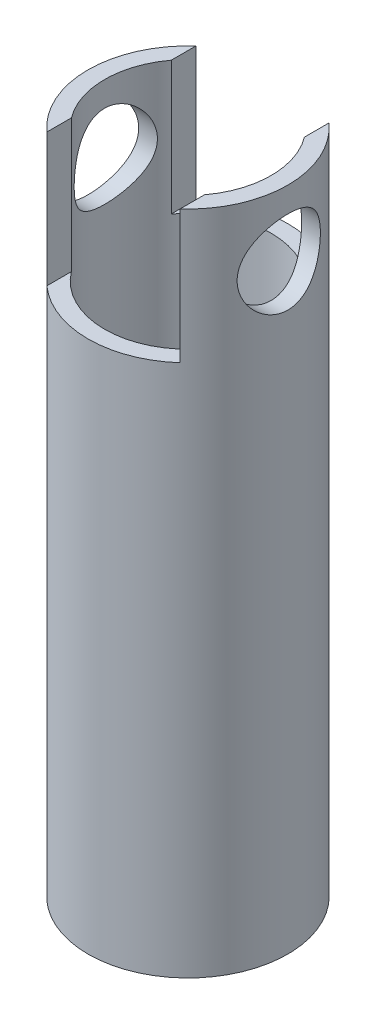
SolidWorks part; units mm, degrees
material "ABS"
ref_plane "Front Plane" through (0, 0, 0) normal (0, 0, 1) x (1, 0, 0)
ref_plane "Top Plane" through (0, 0, 0) normal (0, 1, 0) x (1, 0, 0)
ref_plane "Right Plane" through (0, 0, 0) normal (1, 0, 0) x (0, 0, -1)
sketch "Sketch1" plane through (0, 0, 0) normal (0, 1, 0) x (1, 0, 0)
  circle A0 centre (0, 0) radius 30
  dimension "D1" = 60
extrude "Boss-Extrude1" add sketch "Sketch1" along normal blind 200
sketch "Sketch2" plane through (0, 0, 0) normal (0, 0, 1) x (1, 0, 0)
  line L0 (-30, 200) -> (-20, 200) construction
  line L1 (30, 200) -> (-30, 200) construction
  line L2 (30, 200) -> (20, 200) construction
  line L3 (20, 200) -> (-20, 200)
  line L4 (20, 200) -> (20, 160)
  line L5 (-20, 200) -> (-20, 160)
  line L6 (20, 160) -> (-20, 160)
  dimension "D1" = 10
  dimension "D2" = 40
extrude "Cut-Extrude1" cut sketch "Sketch2" against normal mid plane 150
sketch "Sketch3" plane through (0, 0, 0) normal (0, -1, 0) x (1, 0, 0)
  circle A0 centre (0, 0) radius 25
  circle A1 centre (0, 0) radius 30 construction
  dimension "D1" = 5
extrude "Cut-Extrude2" cut sketch "Sketch3" against normal blind 246
sketch "Sketch4" plane through (0, 0, 0) normal (1, 0, 0) x (0, 0, -1)
  line L0 (0, 200) -> (0, 180) construction
  line L1 (22.3607, 200) -> (-22.3607, 200) construction
  circle A0 centre (0, 180) radius 12.5
  dimension "D2" = 25
  dimension "D1" = 20
extrude "Cut-Extrude3" cut sketch "Sketch4" against normal mid plane 106
